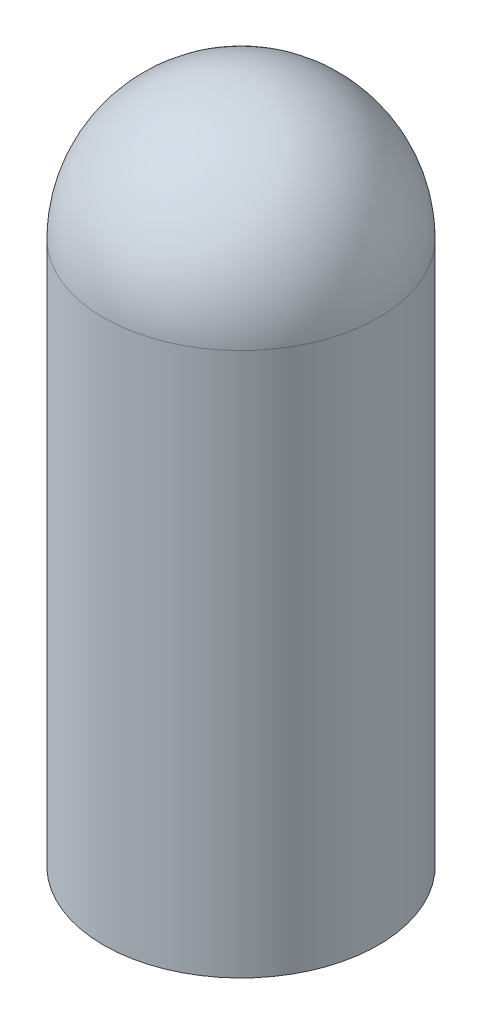
SolidWorks part; units mm, degrees
material "Glass"
ref_plane "Front Plane" through (0, 0, 0) normal (0, 0, 1) x (1, 0, 0)
ref_plane "Top Plane" through (0, 0, 0) normal (0, 1, 0) x (1, 0, 0)
ref_plane "Right Plane" through (0, 0, 0) normal (1, 0, 0) x (0, 0, -1)
sketch "Sketch1" plane through (0, 0, 0) normal (0, 1, 0) x (1, 0, 0)
  circle A0 centre (0, 0) radius 51.3588
  dimension "D1" = 102.7176
extrude "Boss-Extrude1" add sketch "Sketch1" along normal blind 203.2
dome "Dome1" faces to dome 1 distance 50.8 reverse direction no elliptical dome no face at (0, 203.2, 51.3588) parameters "D1"=50.8
shell "Shell1" thickness 0.5588 removed face at (0, 0, 51.3588)
